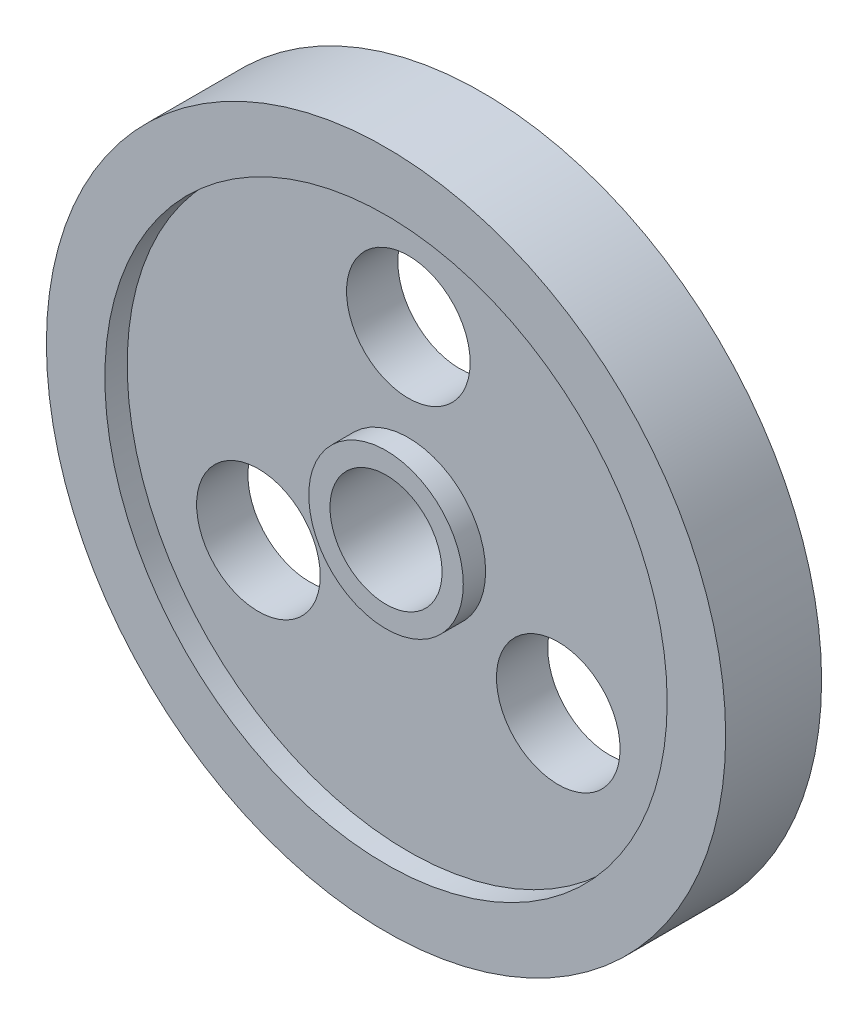
SolidWorks part; units mm, degrees
ref_plane "Front Plane" through (0, 0, 0) normal (0, 0, 1) x (1, 0, 0)
ref_plane "Top Plane" through (0, 0, 0) normal (0, 1, 0) x (1, 0, 0)
ref_plane "Right Plane" through (0, 0, 0) normal (1, 0, 0) x (0, 0, -1)
sketch "Sketch1" plane through (0, 0, 0) normal (0, 0, 1) x (1, 0, 0)
  circle A0 centre (0, 0) radius 19.781
  circle A1 centre (0, 0) radius 3.2639
  dimension "D1" = 39.5619
  dimension "D2" = 6.5278
extrude "Boss-Extrude1" add sketch "Sketch1" along normal mid plane 5.588
sketch "Sketch2" plane through (0, 0, 2.794) normal (0, 0, 1) x (1, 0, 0)
  circle A0 centre (0, 0) radius 16.375
  circle A1 centre (0, 0) radius 4.5
  dimension "D1" = 32.75
  dimension "D2" = 9
extrude "Cut-Extrude1" cut sketch "Sketch2" against normal blind 1.3
mirror "Mirror1" about plane through (0, 0, 0) normal (0, 0, 1) of "Cut-Extrude1"
sketch "Sketch3" plane through (0, 0, 1.494) normal (0, 0, 1) x (1, 0, 0)
  line L0 (0, 0) -> (0, 9.8885)
  circle A0 centre (0, 10.0825) radius 3.6
  circle A1 centre (8.7317, -5.0412) radius 3.6
  circle A2 centre (-8.7317, -5.0412) radius 3.6
  point P9 (0, 0)
  dimension "D1" = 24.6634
  dimension "D2" = 7.2
  dimension "D3" = 3
extrude "Cut-Extrude2" cut sketch "Sketch3" against normal through all contours A2 | A1 | A0 region at (0, 10.0825, 1.494) region at (8.7317, -5.0412, 1.494) region at (-8.7317, -5.0412, 1.494)
